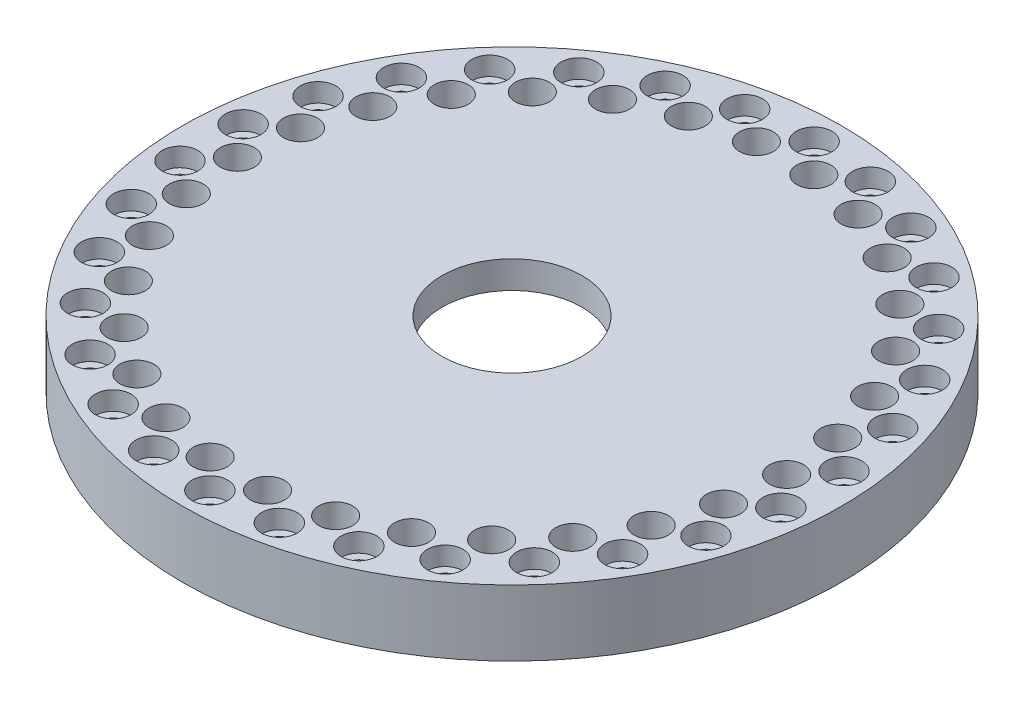
SolidWorks part; units mm, degrees
ref_plane "Front Plane" through (0, 0, 0) normal (0, 0, 1) x (1, 0, 0)
ref_plane "Top Plane" through (0, 0, 0) normal (0, 1, 0) x (1, 0, 0)
ref_plane "Right Plane" through (0, 0, 0) normal (1, 0, 0) x (0, 0, -1)
sketch "Sketch1" plane through (0, 0, 0) normal (0, 1, 0) x (1, 0, 0)
  circle A0 centre (0, 0) radius 60
  circle A3 centre (0, 0) radius 12.75
  dimension "D1" = 120
  dimension "D4" = 25.5
extrude "Boss-Extrude1" add sketch "Sketch1" along normal blind 12
hole_wizard "CBORE for M3 Hex Socket Head Cap Screw1" positions "Sketch2" profile "Sketch4" counterbore size "M3" standard "DIN" end condition through all
sketch "Sketch2" plane through (0, 12, 0) normal (0, 1, 0) x (1, 0, 0)
  point P0 (0, 55)
  point P8 (11.4351, 53.7981)
  point P9 (22.3705, 50.245)
  point P10 (32.3282, 44.4959)
  point P11 (40.873, 36.8022)
  point P12 (47.6314, 27.5)
  point P13 (52.3081, 16.9959)
  point P14 (54.6987, 5.7491)
  point P15 (54.6987, -5.7491)
  point P16 (52.3081, -16.9959)
  point P17 (47.6314, -27.5)
  point P18 (40.873, -36.8022)
  point P19 (32.3282, -44.4959)
  point P20 (22.3705, -50.245)
  point P21 (11.4351, -53.7981)
  point P22 (0, -55)
  point P23 (-11.4351, -53.7981)
  point P24 (-22.3705, -50.245)
  point P25 (-32.3282, -44.4959)
  point P26 (-40.873, -36.8022)
  point P27 (-47.6314, -27.5)
  point P28 (-52.3081, -16.9959)
  point P29 (-54.6987, -5.7491)
  point P30 (-54.6987, 5.7491)
  point P31 (-52.3081, 16.9959)
  point P32 (-47.6314, 27.5)
  point P33 (-40.873, 36.8022)
  point P34 (-32.3282, 44.4959)
  point P35 (-22.3705, 50.245)
  point P36 (-11.4351, 53.7981)
  dimension "D1" = 55
  dimension "D2" = 30
sketch "Sketch4" plane through (0, 12, -55) normal (1, 0, 0) x (0, 0, 1)
  line L0 (0, 0) -> (0, 12)
  line L1 (0, 12) -> (1.8, 12)
  line L3 (1.8, 12) -> (1.8, 3.4)
  line L4 (1.8, 3.4) -> (3.25, 3.4)
  line L5 (3.25, 3.4) -> (3.25, 0)
  line L7 (3.25, 0) -> (0, 0)
  line L11 (0, -6.35) -> (0, 107.95) construction
  dimension "Thru Hole Dia." = 3.6
  dimension "Thru Hole Depth" = 12
  dimension "C'Bore Dia." = 6.5
  dimension "C'Bore Depth" = 3.4
hole_wizard "Ø6.2 (6.2) Diameter Hole1" positions "Sketch5" profile "Sketch6" hole size "Ø6.2" standard "DIN" end condition through all
sketch "Sketch5" plane through (0, 0, 0) normal (0, -1, 0) x (-1, 0, 0)
  line L0 (-11.4351, 53.7981) -> (0, 55) construction
  line L2 (-5.7176, 54.3991) -> (0, 0) construction
  circle A0 centre (0, 0) radius 50 construction
  point P6 (-5.2264, 49.7261)
  point P23 (5.2264, 49.7261)
  point P24 (15.4508, 47.5528)
  point P25 (25, 43.3013)
  point P26 (33.4565, 37.1572)
  point P27 (40.4508, 29.3893)
  point P28 (45.6773, 20.3368)
  point P29 (48.9074, 10.3956)
  point P30 (50, 0)
  point P31 (48.9074, -10.3956)
  point P32 (45.6773, -20.3368)
  point P33 (40.4508, -29.3893)
  point P34 (33.4565, -37.1572)
  point P35 (25, -43.3013)
  point P36 (15.4508, -47.5528)
  point P37 (5.2264, -49.7261)
  point P38 (-5.2264, -49.7261)
  point P39 (-15.4508, -47.5528)
  point P40 (-25, -43.3013)
  point P41 (-33.4565, -37.1572)
  point P42 (-40.4508, -29.3893)
  point P43 (-45.6773, -20.3368)
  point P44 (-48.9074, -10.3956)
  point P45 (-50, 0)
  point P46 (-48.9074, 10.3956)
  point P47 (-45.6773, 20.3368)
  point P48 (-40.4508, 29.3893)
  point P49 (-33.4565, 37.1572)
  point P50 (-25, 43.3013)
  point P51 (-15.4508, 47.5528)
  dimension "D1" = 100
  dimension "D2" = 30
sketch "Sketch6" plane through (15.4508, 0, -47.5528) normal (1, 0, 0) x (0, 0, -1)
  line L0 (0, 0) -> (0, 12)
  line L1 (0, 12) -> (3.1, 12)
  line L2 (3.1, 12) -> (3.1, 0)
  line L5 (3.1, 0) -> (0, 0)
  line L11 (0, -6.35) -> (0, 107.95) construction
  dimension "Thru Hole Dia." = 6.2
  dimension "Thru Hole Depth" = 12
sketch "Sketch7" plane through (0, 0, 0) normal (0, -1, 0) x (1, 0, 0)
  circle A0 centre (0, 0) radius 23.5
  dimension "D1" = 47
extrude "Cut-Extrude1" cut sketch "Sketch7" against normal blind 7
sketch "Sketch8" plane through (0, 7, 0) normal (0, -1, 0) x (1, 0, 0)
  circle A4 centre (0, 0) radius 23.5 construction
  circle A5 centre (0, 0) radius 21.5
  circle A6 centre (0, 0) radius 21.5
  circle A7 centre (0, 0) radius 23.5
  dimension "D1" = 2
extrude "Boss-Extrude2" add sketch "Sketch8" along normal blind 0.6
